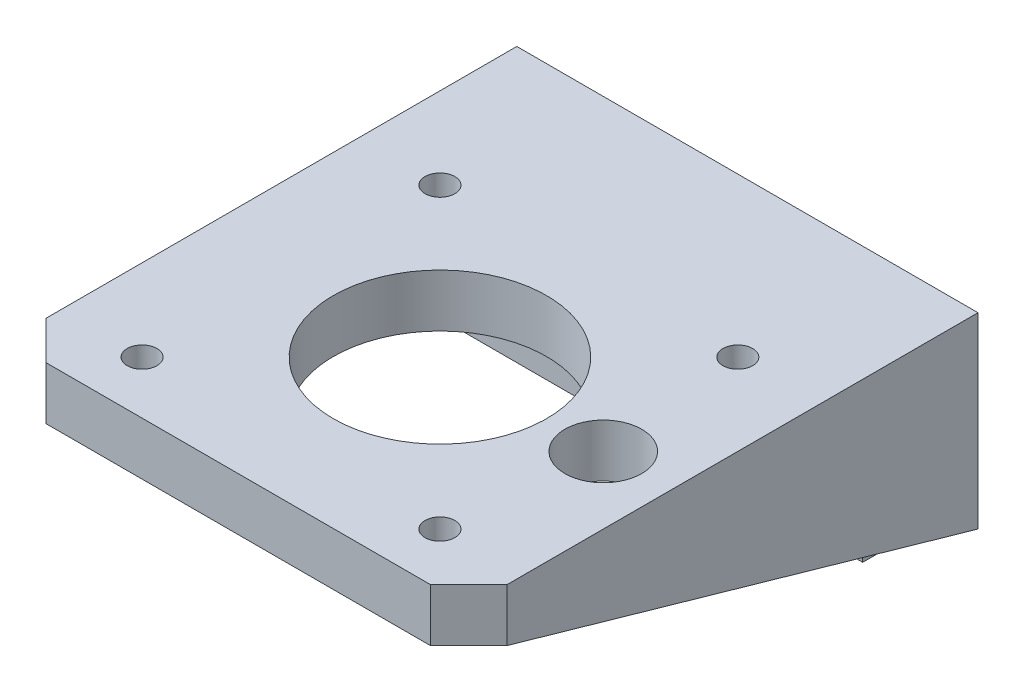
SolidWorks part; units mm, degrees
ref_plane "Alzado" through (0, 0, 0) normal (0, 0, 1) x (1, 0, 0)
ref_plane "Planta" through (0, 0, 0) normal (0, 1, 0) x (1, 0, 0)
ref_plane "Vista lateral" through (0, 0, 0) normal (1, 0, 0) x (0, 0, -1)
sketch "Croquis1" plane through (0, 0, 0) normal (0, 1, 0) x (1, 0, 0)
  line L0 (0, 4) -> (0, 49)
  line L1 (4, 53) -> (44, 53)
  line L2 (48, 49) -> (48, 4)
  line L3 (44, 0) -> (4, 0)
  line L4 (0, 49) -> (4, 53)
  line L5 (44, 53) -> (48, 49)
  line L6 (48, 4) -> (44, 0)
  line L7 (4, 0) -> (0, 4)
  circle A0 centre (8.5, 36.5) radius 1.55
  circle A1 centre (39.5, 36.5) radius 1.55
  circle A2 centre (8.5, 5.5) radius 1.55
  circle A3 centre (39.5, 5.5) radius 1.55
  circle A4 centre (24, 21) radius 11.1
  circle A5 centre (41, 21) radius 4
  point P0 (0, 0)
  point P1 (0, 53)
  point P4 (48, 53)
  point P5 (48, 0)
  dimension "D4" = 3.1
  dimension "D7" = 3.1
  dimension "D14" = 3.1
  dimension "D18" = 3.1
  dimension "D19" = 22.2
  dimension "D22" = 8
  dimension "D1" = 53
  dimension "D2" = 48
  dimension "D3" = 31
  dimension "D5" = 8.5
  dimension "D6" = 16.5
  dimension "D8" = 0
  dimension "D13" = 0
  dimension "D15" = 31
  dimension "D16" = 0
  dimension "D17" = 31
  dimension "D20" = 21
  dimension "D21" = 24
  dimension "D23" = 0
  dimension "D24" = 17
extrude "Saliente-Extruir1" add sketch "Croquis1" along normal blind 5.5
sketch "Croquis3" plane through (0, 5.5, 0) normal (0, 1, 0) x (1, 0, 0)
  line L0 (4, 53) -> (0, 53)
  line L1 (0, 53) -> (0, 49)
  line L10 (4, 53) -> (0, 49)
  line L11 (0, 49) -> (0, 4)
  line L12 (0, 4) -> (4, 0)
  line L13 (4, 0) -> (44, 0)
  line L14 (44, 0) -> (48, 4)
  line L15 (48, 4) -> (48, 49)
  line L16 (48, 49) -> (44, 53)
  line L17 (44, 53) -> (4, 53)
  line L18 (4, 53) -> (0, 49)
  dimension "D1" = 0
extrude "Saliente-Extruir2" add sketch "Croquis3" against normal blind 5.5
sketch "Croquis4" plane through (0, 0, 0) normal (-1, 0, 0) x (0, 0, 1)
  line L2 (-53, 0) -> (-53, 5.5) construction
  line L3 (-53, 0) -> (-53, 5.5)
  line L4 (-53, 0) -> (-53, -14)
  line L5 (-53, -14) -> (-4, 0)
  line L6 (-53, 5.5) -> (-4, 5.5)
  line L7 (-4, 5.5) -> (-4, 0) construction
  line L8 (-4, 5.5) -> (-4, 0)
  dimension "D1" = 14
extrude "Saliente-Extruir3" add sketch "Croquis4" against normal blind 3
sketch "Croquis5" plane through (0, 5.5, 0) normal (0, 1, 0) x (1, 0, 0)
  line L0 (48, 49) -> (48, 53)
  line L1 (48, 53) -> (44, 53)
  line L9 (0, 53) -> (0, 4)
  line L10 (0, 4) -> (4, 0)
  line L11 (4, 0) -> (44, 0)
  line L12 (44, 0) -> (48, 4)
  line L13 (48, 4) -> (48, 49)
  line L14 (48, 49) -> (44, 53)
  line L15 (44, 53) -> (0, 53)
  line L21 (48, 49) -> (44, 53)
  dimension "D1" = 0
extrude "Saliente-Extruir4" add sketch "Croquis5" against normal blind 5.5
sketch "Croquis6" plane through (48, 0, 0) normal (1, 0, 0) x (0, 0, -1)
  line L0 (4, 5.5) -> (4, 0) construction
  line L1 (53, 0) -> (53, 5.5) construction
  line L2 (4, 5.5) -> (53, 5.5) construction
  line L3 (53, 0) -> (53, -14) construction
  line L4 (53, -14) -> (4, 0) construction
  line L5 (4, 5.5) -> (4, 0)
  line L6 (53, 0) -> (53, 5.5)
  line L7 (4, 5.5) -> (53, 5.5)
  line L8 (53, 0) -> (53, -14)
  line L9 (53, -14) -> (4, 0)
extrude "Saliente-Extruir5" add sketch "Croquis6" against normal blind 3
sketch "Croquis7" plane through (0, 0, 0) normal (0, -1, 0) x (1, 0, 0)
  line L0 (45, -53) -> (3, -53)
  line L1 (3, -53) -> (3, -44)
  line L2 (3, -4) -> (3, -53) construction
  line L3 (3, -44) -> (45, -44)
  line L4 (45, -53) -> (45, -21) construction
  line L5 (45, -44) -> (45, -53)
  dimension "D1" = 9
extrude "Saliente-Extruir6" add sketch "Croquis7" along normal blind 14
sketch "Croquis9" plane through (0, 0, -44) normal (0, 0, 1) x (1, 0, 0)
  line L0 (3, -11.4286) -> (3, 0) construction
  line L1 (3, -11.4286) -> (3, 0)
  circle A0 centre (9, -5.7143) radius 1.55
  circle A1 centre (39, -5.7143) radius 1.55
  point P7 (3, -5.7143)
  dimension "D1" = 3.1
  dimension "D2" = 3.1
  dimension "D3" = 0
  dimension "D4" = 30
  dimension "D5" = 0
  dimension "D6" = 6
extrude "Cortar-Extruir1" cut sketch "Croquis9" against normal blind 6 contours A0 | A1 region at (9, -5.7143, -44) region at (39, -5.7143, -44)
sketch "Croquis10" plane through (0, 0, -44) normal (0, 0, 1) x (1, 0, 0)
  circle A0 centre (39, -5.7143) radius 1.55 construction
  circle A1 centre (9, -5.7143) radius 1.55 construction
  circle A2 centre (39, -5.7143) radius 1.55
  circle A3 centre (9, -5.7143) radius 1.55
  circle A4 centre (9, -5.7143) radius 2.8
  circle A5 centre (39, -5.7143) radius 2.8
  circle M1 centre (39, -5.7143) radius 1.55
  circle M2 centre (9, -5.7143) radius 1.55
  dimension "D1" = 5.6
  dimension "D2" = 5.6
extrude "Cortar-Extruir2" cut sketch "Croquis10" against normal blind 3 contours A4 M2 | A5 M1 region at (6.2792, -5.7143, -44) region at (36.2792, -5.7143, -44)
